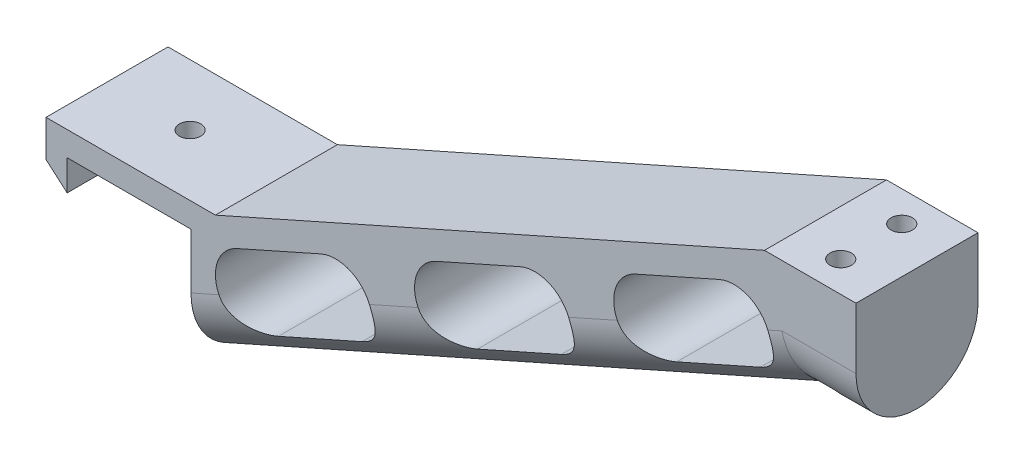
SolidWorks part; units mm, degrees
ref_plane "Plano frontal" through (0, 0, 0) normal (0, 0, 1) x (1, 0, 0)
ref_plane "Plano superior" through (0, 0, 0) normal (0, 1, 0) x (1, 0, 0)
ref_plane "Plano direito" through (0, 0, 0) normal (1, 0, 0) x (0, 0, -1)
sketch "Esboço1" plane through (0, 0, 0) normal (0, 0, 1) x (1, 0, 0)
  line L0 (0, 0) -> (3.4641, -3)
  line L1 (3.4641, -3) -> (3.4641, 2)
  line L2 (3.4641, 2) -> (23.7641, 2)
  line L3 (23.7641, 2) -> (23.7641, -18)
  line L4 (33.7641, -2.4444) -> (47.4713, 3.6476) construction
  line L5 (23.7641, -18) -> (122.7641, 26)
  line L6 (27.7641, 6) -> (117.7641, 46)
  line L8 (117.7641, 46) -> (132.7641, 46)
  line L9 (132.7641, 46) -> (132.7641, 26)
  line L10 (132.7641, 26) -> (122.7641, 26)
  line L13 (27.7641, 6) -> (0, 6)
  line L14 (0, 6) -> (0, 0)
  line L15 (31.3273, 3.0384) -> (45.0344, 9.1305)
  line L16 (36.2009, -7.9273) -> (49.9081, -1.8352)
  line L17 (66.4105, 12.0651) -> (80.1177, 18.1571) construction
  line L18 (63.9737, 17.5479) -> (77.6809, 23.64)
  line L19 (68.8473, 6.5822) -> (82.5545, 12.6743)
  line L20 (99.0569, 26.5746) -> (112.7641, 32.6667) construction
  line L21 (96.6201, 32.0575) -> (110.3273, 38.1495)
  line L22 (101.4938, 21.0917) -> (115.2009, 27.1838)
  arc A0 (31.3273, 3.0384) -> (36.2009, -7.9273) centre (33.7641, -2.4444) ccw
  arc A1 (49.9081, -1.8352) -> (45.0344, 9.1305) centre (47.4713, 3.6476) ccw
  arc A2 (63.9737, 17.5479) -> (68.8473, 6.5822) centre (66.4105, 12.0651) ccw
  arc A3 (82.5545, 12.6743) -> (77.6809, 23.64) centre (80.1177, 18.1571) ccw
  arc A4 (96.6201, 32.0575) -> (101.4938, 21.0917) centre (99.0569, 26.5746) ccw
  arc A5 (115.2009, 27.1838) -> (110.3273, 38.1495) centre (112.7641, 32.6667) ccw
  point P7 (40.6177, 0.6016)
  point P24 (73.2641, 15.1111)
  point P31 (105.9105, 29.6206)
  dimension "D11" = 6
  dimension "D2" = 4
  dimension "D3" = 90
  dimension "D4" = 4
  dimension "D5" = 20.3
  dimension "D6" = 20
  dimension "D7" = 10
  dimension "D8" = 40
  dimension "D9" = 4
  dimension "D10" = 5
  dimension "D12" = 10
  dimension "D13" = 10
  dimension "D14" = 15
  dimension "D16" = 20
  dimension "D17" = 3
  dimension "D15" = 3
extrude "Ressalto-extrusão1" add sketch "Esboço1" along normal mid plane 20
sketch "Esboço7" plane through (0, 2, 0) normal (0, -1, 0) x (1, 0, 0)
  line L0 (3.4641, 10) -> (23.7641, 10) construction
  circle A0 centre (13.6141, 0) radius 1.75
  point P5 (13.6141, 10)
  dimension "D1" = 3.5
extrude "Corte-extrusão3" cut sketch "Esboço7" against normal blind 15
fillet "Filete1" radius 10 4 edges at (73.2641, 4, -10) (73.2641, 4, 10) (127.7641, 26, -10) (127.7641, 26, 10)
sketch "Esboço8" plane through (0, 46, 0) normal (0, 1, 0) x (1, 0, 0)
  line L0 (132.7641, 10) -> (117.7641, 10) construction
  line L1 (132.7641, 0) -> (117.7641, 0) construction
  line L2 (117.7641, -10) -> (117.7641, 10) construction
  circle A0 centre (125.2641, 5) radius 1.75
  circle A1 centre (125.2641, -5) radius 1.75
  point P8 (125.2641, 10)
  dimension "D2" = 3.5
  dimension "D1" = 10
extrude "Corte-extrusão4" cut sketch "Esboço8" against normal through all
sketch "Esboço9" plane through (0, 0, 0) normal (0, 1, 0) x (1, 0, 0)
  line L1 (128.4973, -5) -> (126.8807, -2.2)
  line L2 (126.8807, -2.2) -> (123.6475, -2.2)
  line L3 (123.6475, -2.2) -> (122.0309, -5)
  line L4 (122.0309, -5) -> (123.6475, -7.8)
  line L5 (123.6475, -7.8) -> (126.8807, -7.8)
  line L6 (126.8807, -7.8) -> (128.4973, -5)
  line L7 (128.4973, 5) -> (126.8807, 7.8)
  line L8 (126.8807, 7.8) -> (123.6475, 7.8)
  line L9 (123.6475, 7.8) -> (122.0309, 5)
  line L10 (122.0309, 5) -> (123.6475, 2.2)
  line L11 (123.6475, 2.2) -> (126.8807, 2.2)
  line L12 (126.8807, 2.2) -> (128.4973, 5)
  circle A0 centre (125.2641, -5) radius 2.8 construction
  circle A1 centre (125.2641, 5) radius 2.8 construction
  dimension "D1" = 5.6
extrude "Corte-extrusão5" cut sketch "Esboço9" along normal offset from surface (36 mm away) 10 up to face at (123.5141, 46, 5)
